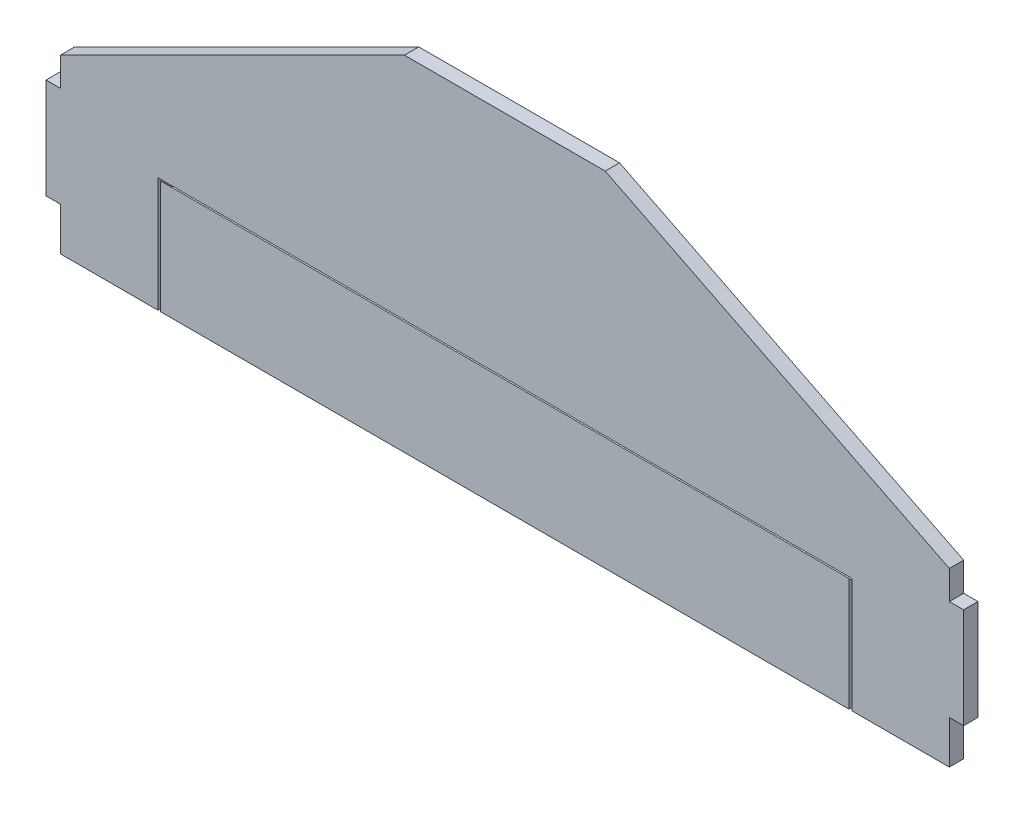
SolidWorks part; units mm, degrees
ref_plane "Ebene vorne" through (0, 0, 0) normal (0, 0, 1) x (1, 0, 0)
ref_plane "Ebene oben" through (0, 0, 0) normal (0, 1, 0) x (1, 0, 0)
ref_plane "Ebene rechts" through (0, 0, 0) normal (1, 0, 0) x (0, 0, -1)
sketch "Skizze1" plane through (0, 0, 0) normal (0, 0, 1) x (1, 0, 0)
  line L0 (0, 0) -> (0, 120) construction
  line L1 (155, 0) -> (-155, 0)
  line L2 (-155, 0) -> (-155, 60)
  line L3 (-155, 60) -> (-35, 120)
  line L4 (-35, 120) -> (35, 120)
  line L5 (155, 0) -> (155, 60)
  line L6 (155, 60) -> (35, 120)
  dimension "D1" = 310
  dimension "D2" = 120
  dimension "D3" = 60
  dimension "D4" = 70
extrude "Grundfläche" add sketch "Skizze1" along normal blind 5
sketch "Skizze3" plane through (0, 0, 5) normal (0, 0, 1) x (1, 0, 0)
  line L0 (0, 0) -> (0, 120) construction
  line L1 (35, 120) -> (-35, 120) construction
  line L2 (155, 0) -> (155, 60) construction
  line L3 (155, 50) -> (160, 50)
  line L4 (155, 50) -> (155, 15)
  line L5 (155, 15) -> (160, 15)
  line L6 (160, 50) -> (160, 15)
  line L7 (-160, 50) -> (-160, 15)
  line L8 (-155, 15) -> (-160, 15)
  line L9 (-155, 50) -> (-155, 15)
  line L10 (-155, 50) -> (-160, 50)
  dimension "D1" = 5
  dimension "D2" = 35
  dimension "D3" = 10
extrude "ZapfenSeitenleitwerk" add sketch "Skizze3" against normal up to surface (5 mm away) up to face at (0, 60, 0)
sketch "Skizze4" plane through (0, 0, 5) normal (0, 0, 1) x (1, 0, 0)
  line L0 (0, 0) -> (0, 40) construction
  line L1 (120, 40) -> (-120, 40) construction
  line L2 (-120, 39.5) -> (-120, 0) construction
  line L3 (-155, 0) -> (155, 0) construction
  line L4 (120, 40) -> (120, 0) construction
  line L5 (-120, 0) -> (-121, 0)
  line L6 (-120, 0) -> (-120, 39.5)
  line L7 (-120, 40) -> (-121, 40)
  line L8 (-121, 0) -> (-121, 40)
  line L9 (121, 0) -> (121, 40)
  line L10 (120, 40) -> (121, 40)
  line L11 (120, 0) -> (120, 39.5)
  line L12 (120, 0) -> (121, 0)
  line L14 (-120, 40) -> (120, 40)
  line L16 (-120, 39.5) -> (120, 39.5)
  dimension "D1" = 1
  dimension "D2" = 40
  dimension "D3" = 240
  dimension "D4" = 0.5
extrude "Schnitt-Linear austragen1" cut sketch "Skizze4" against normal through all
chamfer "Fase1" distance 5 angle 45 1 edges at (0, 39.5, 0)
